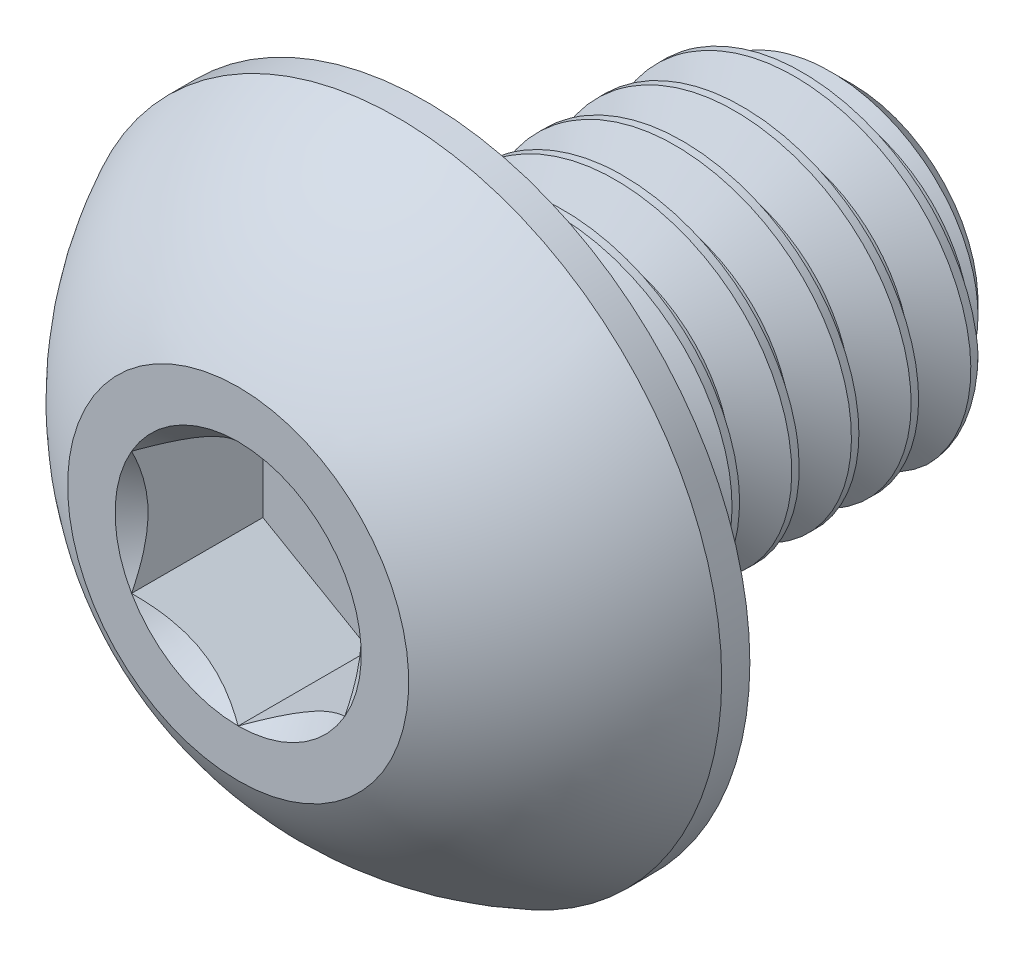
SolidWorks part; units mm, degrees
ref_plane "Front" through (0, 0, 0) normal (0, 0, 1) x (1, 0, 0)
ref_plane "Top" through (0, 0, 0) normal (0, 1, 0) x (1, 0, 0)
ref_plane "Right" through (0, 0, 0) normal (1, 0, 0) x (0, 0, -1)
sketch "Sketch1" plane through (0, 0, 0) normal (1, 0, 0) x (0, 0, -1)
  line L2 (2.2, 2) -> (7.2, 2)
  line L3 (7.2, 2) -> (7.2, 0)
  line L4 (7.2, 0) -> (2.2, 0)
  line L6 (1.87, 3.8) -> (2.2, 3.8) construction
  line L7 (7.2, 2) -> (7.2, -2) construction
  line L8 (0, 0) -> (2.2, 0) construction
  line L9 (2.2, 3.8) -> (2.2, -3.8) construction
  line L11 (2.2, 2) -> (2.2, 0)
  line L13 (0, 1.25) -> (0, -1.25) construction
  line L14 (0, 1.25) -> (0, 2) construction
  arc A3 (0, 2) -> (1.87, 3.8) centre (3.7264, 0) cw construction
  dimension "D1" = 0.33
  dimension "Head Ht" = 2.2
  dimension "Head Dia" = 7.6
  dimension "Dia" = 4
  dimension "Lg" = 5
  dimension "Hex" = 2.5
revolve "Revolve1" add sketch "Sketch1" angle 360 mid plane about L4
sketch "Sketch3" plane through (0, 0, -7.2) normal (0, 0, -1) x (-1, 0, 0)
  circle A0 centre (0, 0) radius 2
curve "Helix/Spiral1" pitch 0.7 height 5.7 radius 2 centre (0, 0, -7.2) axis (0, 0, 1) start towards (0, 1, 0)
sketch "Sketch2" plane through (0, 0, 0) normal (1, 0, 0) x (0, 0, -1)
  line L0 (7.2, 2) -> (7.8125, 2)
  line L1 (7.8125, 2) -> (7.55, 1.5453)
  line L2 (7.55, 1.5453) -> (7.4625, 1.5453)
  line L3 (7.4625, 1.5453) -> (7.2, 2)
  line L4 (7.3312, 1.7727) -> (7.6812, 1.7727) construction
  dimension "D1" = 60
  dimension "D2" = 0.0875
  dimension "D3" = 0.35
chamfer "Chamfer1" distance 0.525 angle 45 1 edges at (0, 2, -7.2)
sweep "Cut-Sweep1" cut profiles "Sketch2" path "Helix/Spiral1" align with end faces yes
sketch "Sketch7" plane through (0, 0, 0) normal (1, 0, 0) x (0, 0, -1)
  line L6 (1.87, 3.8) -> (2.2, 3.8) construction
  line L8 (0, 0) -> (2.2, 0) construction
  line L11 (2.2, 3.8) -> (2.2, -3.8) construction
  line L12 (1.87, 3.8) -> (2.2, 3.8)
  line L13 (0, 0) -> (2.2, 0)
  line L14 (0, 1.25) -> (0, -1.25) construction
  line L15 (2.2, 3.8) -> (2.2, 0)
  line L16 (0, 2) -> (0, 0)
  arc A2 (1.87, 3.8) -> (0, 2) centre (3.7264, 0) ccw construction
  arc A3 (1.87, 3.8) -> (0, 2) centre (3.7264, 0) ccw
revolve "Revolve2" add sketch "Sketch7" angle 360 mid plane about L13
sketch "Sketch5" plane through (0, 0, 0) normal (0, 0, 1) x (1, 0, 0)
  line L1 (1.25, -0.7217) -> (1.25, 0.7217)
  line L2 (1.25, 0.7217) -> (0, 1.4434)
  line L3 (0, 1.4434) -> (-1.25, 0.7217)
  line L4 (-1.25, 0.7217) -> (-1.25, -0.7217)
  line L5 (-1.25, -0.7217) -> (0, -1.4434)
  line L6 (0, -1.4434) -> (1.25, -0.7217)
  circle A0 centre (0, 0) radius 1.25 construction
extrude "Cut-Extrude2" cut sketch "Sketch5" against normal blind 1.54
sketch "Sketch6" plane through (0, 0, 0) normal (0, 0, 1) x (1, 0, 0)
  circle A0 centre (0, 0) radius 1.4434
extrude "Cut-Extrude3" cut sketch "Sketch6" against normal blind 1.54 draft 45
sketch "Sketch9" [suppressed] plane through (0, 0, -6.6) normal (0, 0, 1) x (1, 0, 0)
  circle A2 centre (0, 0) radius 6
extrude "Boss-Extrude2" [suppressed] add sketch "Sketch9" against normal offset from surface (19 mm away) 32 up to face at (0, 1.475, -7.2)
sketch "Sketch10" plane through (0, 0, 0) normal (1, 0, 0) x (0, 0, -1)
  line L0 (7.2, 2) -> (7.2, -2) construction
  point P0 (6.15, -2)
  dimension "D1" = 1.05
equation "\"D3@Helix/Spiral1\" = \"Lg@Sketch1\" + \"D4@Helix/Spiral1\""
equation "\"D2@Sketch2\" = \"D4@Helix/Spiral1\" * .125"
equation "\"D3@Sketch2\" = \"D4@Helix/Spiral1\" * .5"
equation "\"D1@Chamfer1\" = \"D4@Helix/Spiral1\" * .75"
equation "\"D1@Cut-Extrude2\" = \"Head Ht@Sketch1\" * .7"
equation "\"D1@Sketch1\" = \"Head Ht@Sketch1\" * .15"
equation "\"D1@Sketch10\" = \"D4@Helix/Spiral1\" * 1.5"
equation "\"D1@Cut-Extrude3\" = \"D1@Cut-Extrude2\""
